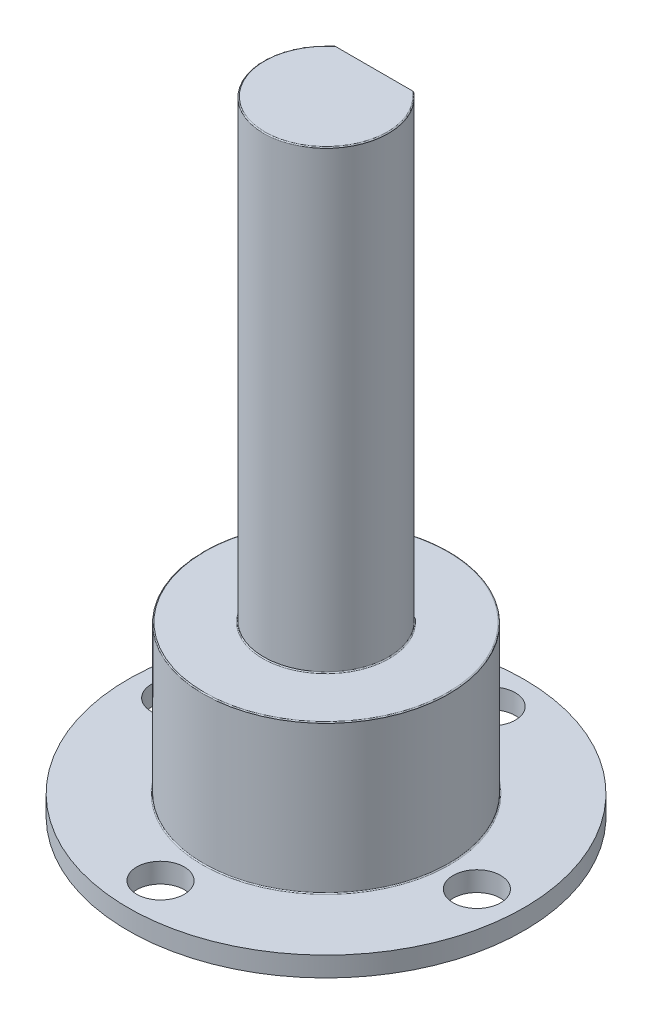
SolidWorks part; units mm, degrees
material "ABS"
ref_plane "Plan de face" through (0, 0, 0) normal (0, 0, 1) x (1, 0, 0)
ref_plane "Plan de dessus" through (0, 0, 0) normal (0, 1, 0) x (1, 0, 0)
ref_plane "Plan de droite" through (0, 0, 0) normal (1, 0, 0) x (0, 0, -1)
sketch "Esquisse2" plane through (0, 0, 0) normal (0, 0, 1) x (1, 0, 0)
  line L0 (0, 31.5) -> (3.15, 31.5)
  line L3 (6.2, 3) -> (6.2, 1)
  line L4 (6.2, 1) -> (10, 1)
  line L5 (10, 1) -> (10, 0)
  line L6 (10, 0) -> (4.5, 0)
  line L7 (4.5, 0) -> (4.5, 5)
  line L8 (4.5, 5) -> (0, 5)
  line L9 (0, 5) -> (0, 31.5)
  line L11 (3.15, 31.5) -> (3.15, 8.5)
  line L12 (3.15, 8.5) -> (6.2, 8.5)
  line L13 (6.2, 3) -> (6.2, 8.5)
  point P2 (1.575, 31.5)
  dimension "D1" = 10
  dimension "D2" = 31.5
  dimension "D3" = 0
  dimension "D4" = 1
  dimension "D5" = 4.5
  dimension "D6" = 2
  dimension "D7" = 8.5
  dimension "D8" = 5
  dimension "D9" = 3.15
  dimension "D10" = 0
  dimension "D12" = 1.7
revolve "Révolution2" add sketch "Esquisse2" angle 360 about L9
sketch "Esquisse3" plane through (0, 31.5, 0) normal (0, 1, 0) x (1, 0, 0)
  line L1 (-3.6413, 2.4219) -> (2.9365, 2.4219)
  line L2 (-3.6413, 2.4219) -> (-3.6413, 3.808)
  line L3 (-3.6413, 3.808) -> (2.9365, 3.808)
  line L4 (2.9365, 2.4219) -> (2.9365, 3.808)
  dimension "D1" = 6.5779
extrude "Enlèv. mat.-Extru.1" cut sketch "Esquisse3" against normal up to surface (23 mm away) contours L4 L3 L2 L1 up to face at (0, 8.5, -3.15)
hole_wizard "Dégagement M21" positions "Esquisse4" profile "Esquisse5" hole size "M2" standard "Ansi Metric" end condition up to next
sketch "Esquisse4" plane through (0, 1, 0) normal (0, 1, 0) x (1, 0, 0)
  circle A0 centre (0, 0) radius 8 construction
  point P0 (0.3713, 7.9914)
  dimension "D1" = 16
sketch "Esquisse5" plane through (0.3713, 1, -7.9914) normal (1, 0, 0) x (0, 0, 1)
  line L0 (0, 0) -> (0, 1.001)
  line L1 (0, 1.001) -> (1.2, 1.001)
  line L2 (1.2, 1.001) -> (1.2, 0)
  line L5 (1.2, 0) -> (0, 0)
  line L11 (0, -6.35) -> (0, 107.95) construction
  dimension "Diamètre du perçage jusqu'au prochain" = 2.4
  dimension "Profondeur du perçage jusqu'au prochain" = 1.001
pattern_circular "Répétition circulaire1" count 4 over 360 about axis through (0, 1, 0) along (0, -1, 0) of "Dégagement M21"
fillet "Congé1" radius 0.05 4 edges at (0, 8.5, 3.15) (0, 8.5, -6.2) (0, 1, -6.2) (0, 31.5, 3.15)
